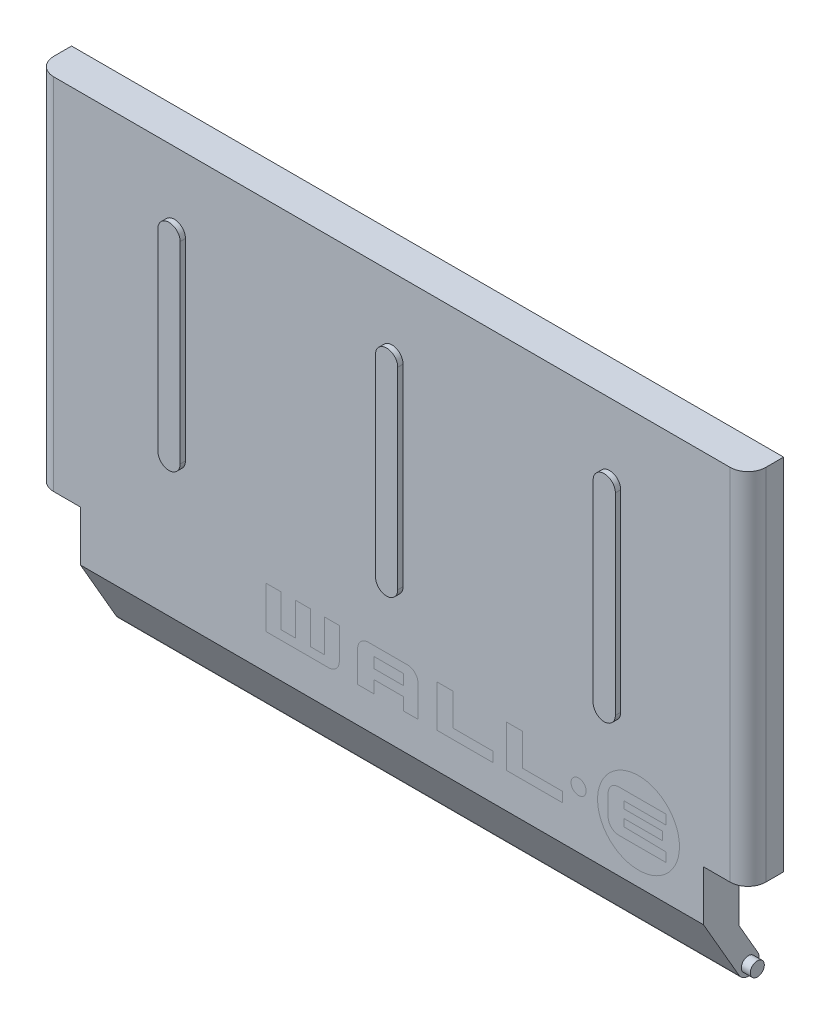
SolidWorks part; units mm, degrees
ref_plane "Front Plane" through (0, 0, 0) normal (0, 0, 1) x (1, 0, 0)
ref_plane "Top Plane" through (0, 0, 0) normal (0, 1, 0) x (1, 0, 0)
ref_plane "Right Plane" through (0, 0, 0) normal (1, 0, 0) x (0, 0, -1)
sketch "Sketch1" plane through (0, 0, 0) normal (0, 0, 1) x (1, 0, 0)
  line L0 (-49.6903, -102.7871) -> (51.9097, -102.7871)
  line L3 (-49.6903, -102.7871) -> (-49.6903, -154.0454)
  line L4 (-49.6903, -154.0454) -> (-43.3403, -154.0454)
  line L5 (-43.3403, -154.0454) -> (-43.3403, -170.0082)
  line L6 (-43.3403, -170.0082) -> (45.5597, -170.0082)
  line L7 (45.5597, -170.0082) -> (45.5597, -154.0454)
  line L9 (45.5597, -154.0454) -> (51.9097, -154.0454)
  line L10 (51.9097, -154.0454) -> (51.9097, -102.7871)
extrude "Extrude1" add sketch "Sketch1" along normal blind 5.08
fillet "Fillet1" radius 2.54 2 edges at (51.9097, -128.4163, 5.08) (-49.6903, -128.4163, 5.08)
chamfer "Chamfer1" distance 5.08 angle 60 1 edges at (1.1097, -170.0082, 5.08) first distance on face at (1.1097, -170.0082, 2.54)
sketch "Sketch3" plane through (45.5597, 0, 0) normal (1, 0, 0) x (0, 0, -1)
  line L0 (-2.6561, -165.4076) -> (0, -170.0082)
  line L1 (-5.08, -161.2093) -> (0, -170.0082) construction
  line L2 (2.6561, -168.4746) -> (0, -163.8741)
  line L3 (0, -170.0082) -> (0, -154.0454) construction
  line L4 (0, -163.8741) -> (-2.6561, -165.4076)
  arc A0 (0, -170.0082) -> (2.6561, -168.4746) centre (1.3281, -169.2414) ccw
extrude "Extrude3" add sketch "Sketch3" against normal up to surface (88.9 mm away) up to face at (-43.3403, -159.8271, 2.54)
sketch "Sketch2" plane through (45.5597, 0, 0) normal (1, 0, 0) x (0, 0, -1)
  circle A0 centre (1.3281, -169.2414) radius 1.004
sketch "Sketch4" plane through (0, 0, 5.08) normal (0, 0, 1) x (1, 0, 0)
  line L0 (1.1097, -113.3685) -> (1.1097, -140.8589) construction
  line L1 (2.6972, -113.3685) -> (2.6972, -140.8589)
  line L2 (-0.4778, -113.3685) -> (-0.4778, -140.8589)
  line L3 (49.3697, -102.7871) -> (-47.1503, -102.7871) construction
  line L4 (-29.9443, -113.3685) -> (-29.9443, -140.8589) construction
  line L5 (-31.5318, -113.3685) -> (-31.5318, -140.8589)
  line L6 (-28.3568, -113.3685) -> (-28.3568, -140.8589)
  line L7 (33.7512, -113.3685) -> (33.7512, -140.8589)
  line L8 (30.5762, -113.3685) -> (30.5762, -140.8589)
  arc A0 (2.6972, -113.3685) -> (-0.4778, -113.3685) centre (1.1097, -113.3685) ccw
  arc A1 (2.6972, -140.8589) -> (-0.4778, -140.8589) centre (1.1097, -140.8589) cw
  arc A2 (-31.5318, -113.3685) -> (-28.3568, -113.3685) centre (-29.9443, -113.3685) cw
  arc A3 (-31.5318, -140.8589) -> (-28.3568, -140.8589) centre (-29.9443, -140.8589) ccw
  arc A4 (33.7512, -113.3685) -> (30.5762, -113.3685) centre (32.1637, -113.3685) ccw
  arc A5 (33.7512, -140.8589) -> (30.5762, -140.8589) centre (32.1637, -140.8589) cw
  point P8 (1.1097, -102.7871)
  dimension "D1" = 1.5875
  dimension "D2" = 1.5875
  dimension "D3" = 1.5875
  dimension "D4" = 1.5875
extrude "Extrude4" add sketch "Sketch4" along normal blind 0.762
sketch "Sketch5" plane through (0, 0, 5.08) normal (0, 0, 1) x (1, 0, 0)
  line L0 (-16.8839, -150.2139) -> (-16.8839, -156.1947)
  line L1 (-16.8839, -156.1947) -> (-7.9276, -156.1947)
  line L2 (-6.4036, -154.6707) -> (-6.4036, -150.2139)
  line L3 (-6.4036, -150.2139) -> (-8.5448, -150.2139)
  line L4 (-8.5448, -150.2139) -> (-8.5448, -154.8945)
  line L5 (-8.5448, -154.8945) -> (-10.5319, -154.8945)
  line L6 (-10.5319, -154.8945) -> (-10.5319, -150.2139)
  line L7 (-10.5319, -150.2139) -> (-12.6419, -150.2139)
  line L8 (-12.6419, -150.2139) -> (-12.6419, -154.8945)
  line L9 (-12.6419, -154.8945) -> (-14.6905, -154.8945)
  line L10 (-14.6905, -154.8945) -> (-14.6905, -150.2139)
  line L11 (-14.6905, -150.2139) -> (-16.8839, -150.2139)
  line L12 (-3.7845, -156.1947) -> (-1.4889, -156.1947)
  line L13 (-1.4889, -156.1947) -> (-1.4889, -154.429)
  line L14 (-1.4889, -154.429) -> (2.7339, -154.429)
  line L15 (2.7339, -154.429) -> (2.7339, -156.1947)
  line L16 (2.7339, -156.1947) -> (4.8311, -156.1947)
  line L17 (4.8311, -156.1947) -> (4.8311, -151.7379)
  line L18 (3.3071, -150.2139) -> (-2.2605, -150.2139)
  line L19 (-3.7845, -151.7379) -> (-3.7845, -156.1947)
  line L20 (7.5718, -150.2139) -> (7.5718, -156.1947)
  line L21 (-1.4889, -153.0687) -> (2.7339, -153.0687)
  line L22 (-1.4889, -153.0687) -> (-1.4889, -151.5666)
  line L23 (-1.4889, -151.5666) -> (2.7339, -151.5666)
  line L24 (2.7339, -153.0687) -> (2.7339, -151.5666)
  line L25 (7.5718, -156.1947) -> (15.5296, -156.1947)
  line L26 (15.5296, -156.1947) -> (15.5296, -154.7801)
  line L27 (15.5296, -154.7801) -> (9.8494, -154.7801)
  line L28 (9.8494, -154.7801) -> (9.8494, -150.2139)
  line L29 (9.8494, -150.2139) -> (7.5718, -150.2139)
  line L30 (17.4616, -150.2139) -> (17.4616, -156.1947)
  line L31 (17.4616, -156.1947) -> (25.4194, -156.1947)
  line L32 (25.4194, -156.1947) -> (25.4194, -154.7801)
  line L33 (25.4194, -154.7801) -> (19.7392, -154.7801)
  line L34 (19.7392, -154.7801) -> (19.7392, -150.2139)
  line L35 (19.7392, -150.2139) -> (17.4616, -150.2139)
  line L36 (40.2128, -150.2139) -> (40.2128, -151.5666)
  line L37 (40.2128, -151.5666) -> (34.254, -151.5666)
  line L38 (34.254, -151.5666) -> (34.254, -152.5678)
  line L39 (34.254, -152.5678) -> (39.7162, -152.5678)
  line L40 (39.7162, -152.5678) -> (39.7162, -153.7519)
  line L41 (39.7162, -153.7519) -> (34.254, -153.7519)
  line L42 (34.254, -153.7519) -> (34.254, -154.7801)
  line L43 (34.254, -154.7801) -> (40.2128, -154.8945)
  line L44 (40.2128, -154.8945) -> (40.2128, -156.1947)
  line L45 (40.2128, -156.1947) -> (33.4832, -156.1947)
  line L46 (31.9592, -154.6707) -> (31.9592, -151.7379)
  line L47 (33.4832, -150.2139) -> (40.2128, -150.2139)
  arc A0 (-7.9276, -156.1947) -> (-6.4036, -154.6707) centre (-7.9276, -154.6707) ccw
  arc A1 (-2.2605, -150.2139) -> (-3.7845, -151.7379) centre (-2.2605, -151.7379) ccw
  arc A2 (4.8311, -151.7379) -> (3.3071, -150.2139) centre (3.3071, -151.7379) ccw
  circle A3 centre (27.7404, -153.0687) radius 1.0785
  arc A4 (31.9592, -151.7379) -> (33.4832, -150.2139) centre (33.4832, -151.7379) cw
  arc A5 (33.4832, -156.1947) -> (31.9592, -154.6707) centre (33.4832, -154.6707) cw
  circle A6 centre (36.2921, -153.2611) radius 5.8429
  dimension "D1" = 1.524
  dimension "D2" = 1.524
  dimension "D3" = 1.524
surface "Surface-Extrude1" sketch "Sketch5" parameters "D1"=1.27
split line "Split Line1"
delete or keep bodies "Body-Delete1" type delete bodies bodies 105 106 107 108 109 110 111 112
extrude "Saliente-Extruir1" add sketch "Sketch2" along normal blind 1.27 and the other way blind 90.17
